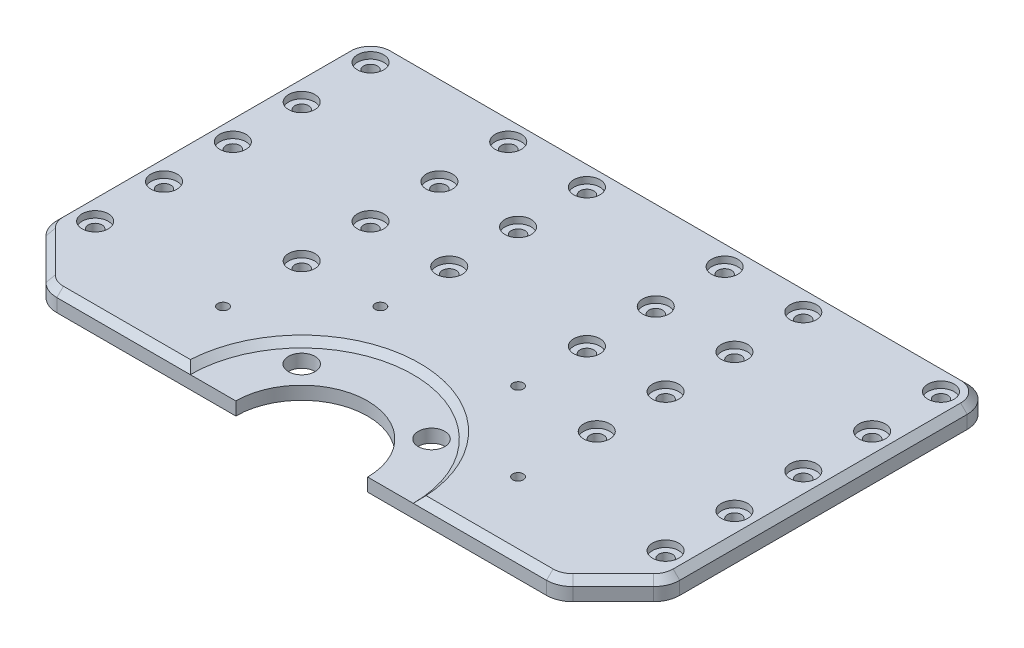
SolidWorks part; units mm, degrees
material "ABS"
ref_plane "正面" through (0, 0, 0) normal (0, 0, 1) x (1, 0, 0)
ref_plane "平面" through (0, 0, 0) normal (0, 1, 0) x (1, 0, 0)
ref_plane "右側面" through (0, 0, 0) normal (1, 0, 0) x (0, 0, -1)
sketch "ｽｹｯﾁ1" plane through (0, 0, 0) normal (0, 1, 0) x (1, 0, 0)
  line L0 (-10.05, 0) -> (-39, 0)
  line L1 (-39, 0) -> (-47.5, 8.5)
  line L2 (-47.5, 8.5) -> (-47.5, 58)
  line L3 (-47.5, 58) -> (47.5, 58)
  line L4 (47.5, 58) -> (47.5, 8.5)
  line L5 (47.5, 8.5) -> (39, 0)
  line L6 (39, 0) -> (10.05, 0)
  line L7 (-10.05, 0) -> (0, 0) construction
  line L8 (0, 0) -> (10.05, 0) construction
  arc A0 (10.05, 0) -> (-10.05, 0) centre (0, 0) ccw
  dimension "D1" = 20.1
  dimension "D2" = 95
  dimension "D3" = 58
  dimension "D4" = 78
extrude "ﾎﾞｽ - 押し出し1" add sketch "ｽｹｯﾁ1" along normal blind 3
hole_wizard "M2 なべ頭ねじ用座ぐり穴1" positions "ｽｹｯﾁ2" profile "ｽｹｯﾁ3" counterbore size "M2" standard "ISO"
sketch "ｽｹｯﾁ2" plane through (0, 3, 0) normal (0, 1, 0) x (1, 0, 0)
  line L0 (-43.5, 54) -> (-22.5, 54) construction
  line L2 (47.5, 58) -> (-47.5, 58) construction
  line L3 (-47.5, 58) -> (-47.5, 8.5) construction
  point P0 (-43.5, 54)
  point P2 (-22.5, 54)
  dimension "D1" = 4
  dimension "D2" = 4
  dimension "D3" = 21
sketch "ｽｹｯﾁ3" plane through (-43.5, 3, -54) normal (1, 0, 0) x (0, 0, 1)
  line L0 (0, 0) -> (0, 4.6309)
  line L1 (0, 4.6309) -> (1.05, 4)
  line L2 (1.05, 4) -> (1.05, 1)
  line L3 (1.05, 1) -> (2, 1)
  line L4 (2, 1) -> (2, 0)
  line L5 (2, 0) -> (0, 0)
  line L10 (0, 4.6309) -> (-1.05, 4) construction
  line L11 (0, -6.35) -> (0, 107.95) construction
  dimension "穴の直径" = 2.1
  dimension "穴の深さ" = 4
  dimension "座ぐり穴の直径" = 4
  dimension "座ぐり穴の深さ" = 1
  dimension "ﾄﾞﾘﾙ角度" = 118
pattern_linear "直線ﾊﾟﾀｰﾝ1" count 3 spacing 33 along (1, 0, 0) of "M2 なべ頭ねじ用座ぐり穴1"
pattern_linear "直線ﾊﾟﾀｰﾝ2" count 3 spacing 10.5 along (0, 0, 1) of "M2 なべ頭ねじ用座ぐり穴1", "直線ﾊﾟﾀｰﾝ1"
pattern_linear "直線ﾊﾟﾀｰﾝ3" count 2 spacing 31.5 along (0, 0, 1) of "M2 なべ頭ねじ用座ぐり穴1"
hole_wizard "M2 ねじ穴1" positions "ｽｹｯﾁ4" profile "ｽｹｯﾁ5" tap size "M2" standard "ISO"
sketch "ｽｹｯﾁ4" plane through (0, 3, 0) normal (0, 1, 0) x (1, 0, 0)
  line L0 (-22.5, 10.5) -> (-22.5, 22.5) construction
  line L1 (-22.5, 22.5) -> (-10.5, 22.5) construction
  line L2 (-10.5, 22.5) -> (-10.5, 33) construction
  line L4 (-39, 0) -> (-10.05, 0) construction
  point P0 (-10.5, 22.5)
  point P2 (-22.5, 10.5)
  dimension "D1" = 10.5
sketch "ｽｹｯﾁ5" plane through (-10.5, 3, -22.5) normal (1, 0, 0) x (0, 0, 1)
  line L0 (0, 0) -> (0, 6.4807)
  line L1 (0, 6.4807) -> (0.8, 6)
  line L2 (0.8, 6) -> (0.8, 0)
  line L5 (0.8, 0) -> (0, 0)
  line L10 (0, 6.4807) -> (-0.8, 6) construction
  line L11 (0, -6.35) -> (0, 107.95) construction
  dimension "ねじ下穴ﾄﾞﾘﾙ直径" = 1.6
  dimension "ねじ下穴ﾄﾞﾘﾙの深さ" = 6
  dimension "ﾄﾞﾘﾙ角度" = 118
cosmetic thread "穴のねじ山1" parameters "D1"=4, "D2"=2
cosmetic thread "穴のねじ山2" parameters "D1"=4, "D2"=2
hole_wizard "M2 なべ頭ねじ用座ぐり穴2" positions "ｽｹｯﾁ6" profile "ｽｹｯﾁ7" counterbore size "M2" standard "ISO"
sketch "ｽｹｯﾁ6" plane through (0, 3, 0) normal (0, 1, 0) x (1, 0, 0)
  line L0 (-43.5, 22.5) -> (-43.5, 12) construction
  line L3 (-43.5, 33) -> (-43.5, 22.5) construction
  point P0 (-43.5, 12)
sketch "ｽｹｯﾁ7" plane through (-43.5, 3, -12) normal (1, 0, 0) x (0, 0, 1)
  line L0 (0, 0) -> (0, 6.6309)
  line L1 (0, 6.6309) -> (1.05, 6)
  line L2 (1.05, 6) -> (1.05, 1)
  line L3 (1.05, 1) -> (2, 1)
  line L4 (2, 1) -> (2, 0)
  line L5 (2, 0) -> (0, 0)
  line L10 (0, 6.6309) -> (-1.05, 6) construction
  line L11 (0, -6.35) -> (0, 107.95) construction
  dimension "穴の直径" = 2.1
  dimension "穴の深さ" = 6
  dimension "座ぐり穴の直径" = 4
  dimension "座ぐり穴の深さ" = 1
  dimension "ﾄﾞﾘﾙ角度" = 118
mirror "ﾐﾗｰ1" about plane through (0, 0, 0) normal (1, 0, 0) of "M2 なべ頭ねじ用座ぐり穴2", "M2 ねじ穴1", "直線ﾊﾟﾀｰﾝ3"
cosmetic thread "穴のねじ山3" parameters "D1"=4, "D2"=2
cosmetic thread "穴のねじ山4" parameters "D1"=4, "D2"=2
sketch "ｽｹｯﾁ8" plane through (0, 3, 0) normal (0, 1, 0) x (1, 0, 0)
  circle A0 centre (0, 0) radius 17
  dimension "D1" = 34
extrude "ｶｯﾄ - 押し出し1" cut sketch "ｽｹｯﾁ8" against normal blind 1
sketch "ｽｹｯﾁ9" plane through (0, 2, 0) normal (0, 1, 0) x (1, 0, 0)
  line L0 (-9.8995, 9.8995) -> (0, 0) construction
  line L2 (-17, 0) -> (-10.05, 0) construction
  circle A0 centre (-9.8995, 9.8995) radius 2.025
  dimension "D1" = 4.05
  dimension "D2" = 45
  dimension "D3" = 14
extrude "ｶｯﾄ - 押し出し2" cut sketch "ｽｹｯﾁ9" against normal through all
pattern_circular "円形ﾊﾟﾀｰﾝ1" count 2 every 90 about axis through (0, 3, 0) along (0, -1, 0) of "ｶｯﾄ - 押し出し2"
fillet "ﾌｨﾚｯﾄ1" radius 4 6 edges at (-47.5, 1.5, -8.5) (-39, 1.5, 0) (39, 1.5, 0) (47.5, 1.5, -8.5) (47.5, 1.5, -58) (-47.5, 1.5, -58)
chamfer "面取り1" distance 1 angle 45 14 edges at (0, 3, -17) (27.1716, 3, 0) (38.8739, 3, -0.3045) (43.25, 3, -4.25) (47.1955, 3, -8.6261) (47.5, 3, -32.0784) (-27.1716, 3, 0) (46.3284, 3, -56.8284) (-38.8739, 3, -0.3045) (0, 3, -58) (-43.25, 3, -4.25) (-46.3284, 3, -56.8284) (-47.1955, 3, -8.6261) (-47.5, 3, -32.0784)
